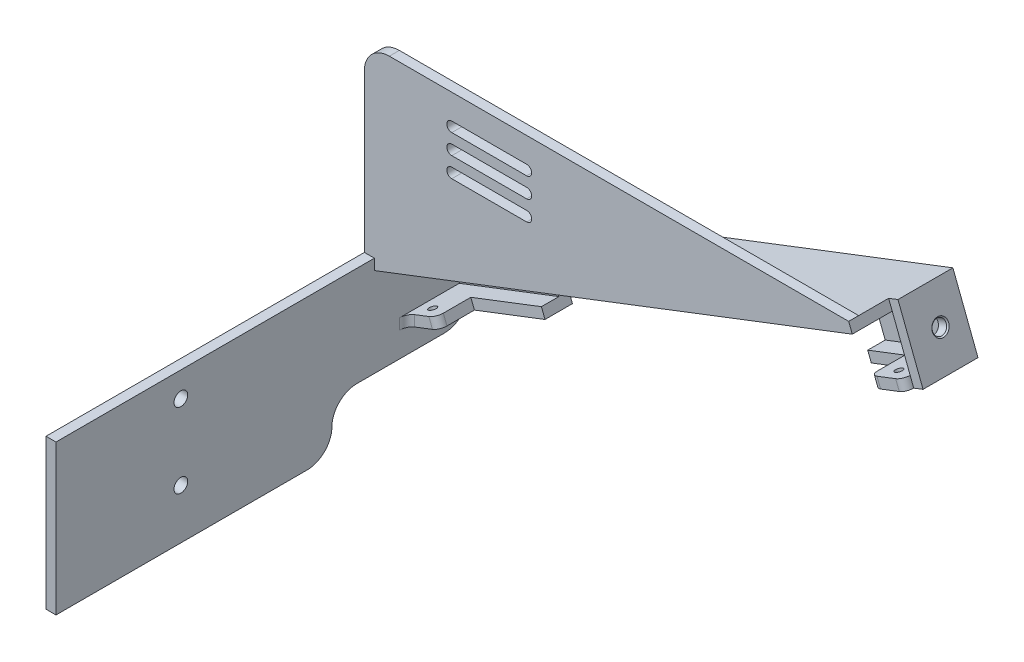
SolidWorks part; units mm, degrees
ref_plane "前视基准面" through (0, 0, 0) normal (0, 0, 1) x (1, 0, 0)
ref_plane "上视基准面" through (0, 0, 0) normal (0, 1, 0) x (1, 0, 0)
ref_plane "右视基准面" through (0, 0, 0) normal (1, 0, 0) x (0, 0, -1)
other "Configuration Table"
sketch "草图1" plane through (0, 0, 0) normal (1, 0, 0) x (0, 0, -1)
  line L1 (0, 0) -> (165.5, 0)
  line L2 (0, 0) -> (0, 60)
  line L3 (0, 60) -> (165.5, 60)
  line L4 (165.5, 0) -> (165.5, 60)
  dimension "D1" = 60
  dimension "D2" = 165.5
extrude "凸台-拉伸1" add sketch "草图1" along normal blind 4
sketch "草图2" plane through (0, 0, -165.5) normal (0, 0, -1) x (-1, 0, 0)
  line L0 (-4, 30) -> (-204, 106.9309)
  line L1 (-4, 0) -> (-4, 60) construction
  line L2 (-204, 106.9309) -> (-193.9477, 133.0643)
  line L6 (-4, 30) -> (-4, 60)
  line L7 (-4, 60) -> (-193.9477, 133.0643)
  dimension "D1" = 28
  dimension "D2" = 200
extrude "凸台-拉伸2" add sketch "草图2" against normal blind 4
sketch "草图3" plane through (-9.5368, 24.793, 0) normal (0.359, -0.9333, 0) x (0.9333, 0.359, 0)
  line L12 (228.7894, -165.5) -> (228.7894, -140.5)
  line L13 (228.7894, -140.5) -> (14.5037, -140.5)
  line L14 (14.5037, -165.5) -> (14.5037, -140.5)
  line L15 (14.5037, -161.5) -> (14.5037, -165.5) construction
  line L20 (14.5037, -165.5) -> (228.7894, -165.5)
  line L21 (228.7894, -165.5) -> (228.7894, -161.5)
  line L22 (228.7894, -161.5) -> (14.5037, -161.5)
  line L23 (14.5037, -161.5) -> (14.5037, -165.5)
  line L24 (14.5037, -165.5) -> (228.7894, -165.5)
  dimension "D1" = 25
  dimension "D2" = 0
extrude "凸台-拉伸5" add sketch "草图3" against normal blind 4
sketch "草图4" plane through (4, 0, 0) normal (1, 0, 0) x (0, 0, -1)
  line L0 (0, 60) -> (0, 0) construction
  line L1 (0, 50) -> (50, 50) construction
  line L2 (0, 50) -> (0, 20) construction
  line L3 (0, 20) -> (50, 20) construction
  line L4 (50, 50) -> (50, 20) construction
  line L5 (161.5, 60) -> (0, 60) construction
  circle A0 centre (50, 50) radius 2.75
  circle A1 centre (50, 20) radius 2.75
  dimension "D4" = 5.5
  dimension "D5" = 5.5
  dimension "D1" = 30
  dimension "D2" = 10
  dimension "D3" = 50
extrude "切除-拉伸1" cut sketch "草图4" against normal blind 4
sketch "草图5" plane through (4, 0, 0) normal (1, 0, 0) x (0, 0, -1)
  line L1 (165.5, 0) -> (110.5, 0)
  line L2 (165.5, 0) -> (165.5, 20)
  line L3 (165.5, 20) -> (110.5, 20)
  line L4 (110.5, 0) -> (110.5, 20)
  dimension "D1" = 55
  dimension "D2" = 20
extrude "切除-拉伸2" cut sketch "草图5" against normal blind 4
fillet "圆角1" radius 10 3 edges at (2, 20, -165.5) (2, 20, -110.5) (2, 0, -110.5)
sketch "草图6" plane through (-9.5368, 24.793, 0) normal (0.359, -0.9333, 0) x (0.9333, 0.359, 0)
  line L0 (228.7894, -140.5) -> (14.5037, -140.5) construction
  line L1 (28.5037, -140.5) -> (214.7894, -140.5)
  line L2 (28.5037, -140.5) -> (28.5037, -154.5)
  line L3 (28.5037, -154.5) -> (214.7894, -154.5)
  line L4 (214.7894, -140.5) -> (214.7894, -154.5)
  line L5 (228.7894, -140.5) -> (228.7894, -165.5) construction
  line L6 (14.5037, -140.5) -> (14.5037, -165.5) construction
  dimension "D1" = 14
  dimension "D2" = 14
  dimension "D3" = 14
extrude "切除-拉伸3" cut sketch "草图6" against normal blind 4
sketch "草图7" plane through (-9.5368, 24.793, 0) normal (0.359, -0.9333, 0) x (0.9333, 0.359, 0)
  line L0 (228.7894, -140.5) -> (228.7894, -165.5) construction
  circle A0 centre (221.7894, -145.5) radius 1.5
  circle A1 centre (21.7894, -145.5) radius 1.5
  dimension "D1" = 200
  dimension "D3" = 3
  dimension "D4" = 3
  dimension "D2" = 145.5
  dimension "D5" = 7
extrude "切除-拉伸4" cut sketch "草图7" against normal blind 4
fillet "圆角2" radius 3 4 edges at (16.3486, 36.8928, -140.5) (4, 32.1429, -140.5) (203.282, 108.7976, -140.5) (190.2153, 103.7714, -140.5)
sketch "草图8" plane through (0, 0, -161.5) normal (0, 0, 1) x (1, 0, 0)
  line L0 (45.3333, 45.8991) -> (39.9482, 59.8991)
  line L2 (39.9482, 59.8991) -> (170.6148, 110.1606)
  line L3 (170.6148, 110.1606) -> (176, 96.1606)
  line L4 (176, 96.1606) -> (45.3333, 45.8991)
  line L5 (193.9477, 133.0643) -> (202.564, 110.6643) construction
  line L6 (17.0667, 35.0262) -> (190.9333, 101.9048) construction
  dimension "D1" = 140
  dimension "D2" = 15
  dimension "D3" = 30
extrude "切除-拉伸5" cut sketch "草图8" against normal through all
sketch "草图9" plane through (0, 0, -161.5) normal (0, 0, -1) x (-1, 0, 0)
  line L4 (-43.8973, 49.6324) -> (-174.564, 99.8939)
  line L5 (-174.564, 99.8939) -> (-176, 96.1606)
  line L6 (-176, 96.1606) -> (-45.3333, 45.8991)
  line L7 (-45.3333, 45.8991) -> (-43.8973, 49.6324)
  line L8 (-43.8973, 49.6324) -> (-174.564, 99.8939)
  line L9 (-174.564, 99.8939) -> (-176, 96.1606)
  line L10 (-176, 96.1606) -> (-45.3333, 45.8991)
  line L11 (-45.3333, 45.8991) -> (-43.8973, 49.6324)
  dimension "D1" = 0
extrude "切除-拉伸6" cut sketch "草图9" against normal blind 10
sketch "草图11" plane through (-19.5891, 50.9264, 0) normal (-0.359, 0.9333, 0) x (0.9333, 0.359, 0)
  line L0 (21.5407, 165.5) -> (21.5407, 0) construction
  line L1 (228.7894, 165.5) -> (21.5407, 165.5)
  line L2 (228.7894, 165.5) -> (228.7894, 131.5)
  line L3 (228.7894, 131.5) -> (21.5407, 131.5)
  line L4 (21.5407, 165.5) -> (21.5407, 131.5)
  dimension "D1" = 34
extrude "凸台-拉伸6" add sketch "草图11" against normal blind 4
sketch "草图12" plane through (0, 0, -131.5) normal (0, 0, 1) x (1, 0, 0)
  line L0 (4, 55.7143) -> (4, 60)
  line L1 (4, 60) -> (0, 60)
  line L2 (0, 60) -> (0, 133.0643)
  line L3 (0, 133.0643) -> (193.9477, 133.0643)
  line L4 (193.9477, 133.0643) -> (195.3837, 129.3309)
  line L5 (195.3837, 129.3309) -> (4, 55.7143)
extrude "凸台-拉伸7" add sketch "草图12" along normal blind 4
fillet "圆角3" radius 10 1 edges at (0, 133.0643, -129.5)
sketch "草图14" plane through (0, 0, -131.5) normal (0, 0, -1) x (-1, 0, 0)
  line L0 (-65, 121.0643) -> (-35, 121.0643) construction
  line L1 (-65, 123.0643) -> (-35, 123.0643)
  line L2 (-65, 119.0643) -> (-35, 119.0643)
  line L3 (-193.9477, 133.0643) -> (-10, 133.0643) construction
  line L4 (0, 123.0643) -> (0, 60) construction
  line L5 (-65, 113.0643) -> (-35, 113.0643) construction
  line L6 (-65, 115.0643) -> (-35, 115.0643)
  line L7 (-65, 111.0643) -> (-35, 111.0643)
  line L8 (-65, 105.0643) -> (-35, 105.0643) construction
  line L9 (-65, 107.0643) -> (-35, 107.0643)
  line L10 (-65, 103.0643) -> (-35, 103.0643)
  arc A0 (-65, 123.0643) -> (-65, 119.0643) centre (-65, 121.0643) ccw
  arc A1 (-35, 119.0643) -> (-35, 123.0643) centre (-35, 121.0643) ccw
  arc A2 (-65, 115.0643) -> (-65, 111.0643) centre (-65, 113.0643) ccw
  arc A3 (-35, 111.0643) -> (-35, 115.0643) centre (-35, 113.0643) ccw
  arc A4 (-65, 107.0643) -> (-65, 103.0643) centre (-65, 105.0643) ccw
  arc A5 (-35, 103.0643) -> (-35, 107.0643) centre (-35, 105.0643) ccw
  point P2 (-50, 121.0643)
  point P14 (-50, 113.0643)
  point P21 (-50, 105.0643)
  dimension "D2" = 2
  dimension "D1" = 30
  dimension "D3" = 10
  dimension "D4" = 35
  dimension "D5" = 3
extrude "切除-拉伸7" cut sketch "草图14" against normal blind 4
sketch "草图15" plane through (213.5368, 82.1379, 0) normal (0.9333, 0.359, 0) x (0, 0, -1)
  line L0 (165.5, 54.564) -> (131.5, 54.564) construction
  line L1 (165.5, 26.564) -> (143.5, 26.564)
  line L2 (165.5, 26.564) -> (165.5, 54.564)
  line L3 (165.5, 54.564) -> (143.5, 54.564)
  line L4 (143.5, 26.564) -> (143.5, 54.564)
  dimension "D1" = 22
extrude "凸台-拉伸8" add sketch "草图15" along normal blind 4
sketch "草图16" plane through (217.2701, 83.5739, 0) normal (0.9333, 0.359, 0) x (0, 0, -1)
  line L0 (165.5, 26.564) -> (165.5, 54.564) construction
  line L1 (143.5, 26.564) -> (165.5, 26.564) construction
  circle A0 centre (155.5, 40.564) radius 2.75
  dimension "D1" = 5.5
  dimension "D2" = 10
  dimension "D3" = 14
extrude "切除-拉伸8" cut sketch "草图16" against normal blind 10
chamfer "倒角1" distance 0.5 angle 45 1 edges at (201.7199, 124.0003, -155.5)
